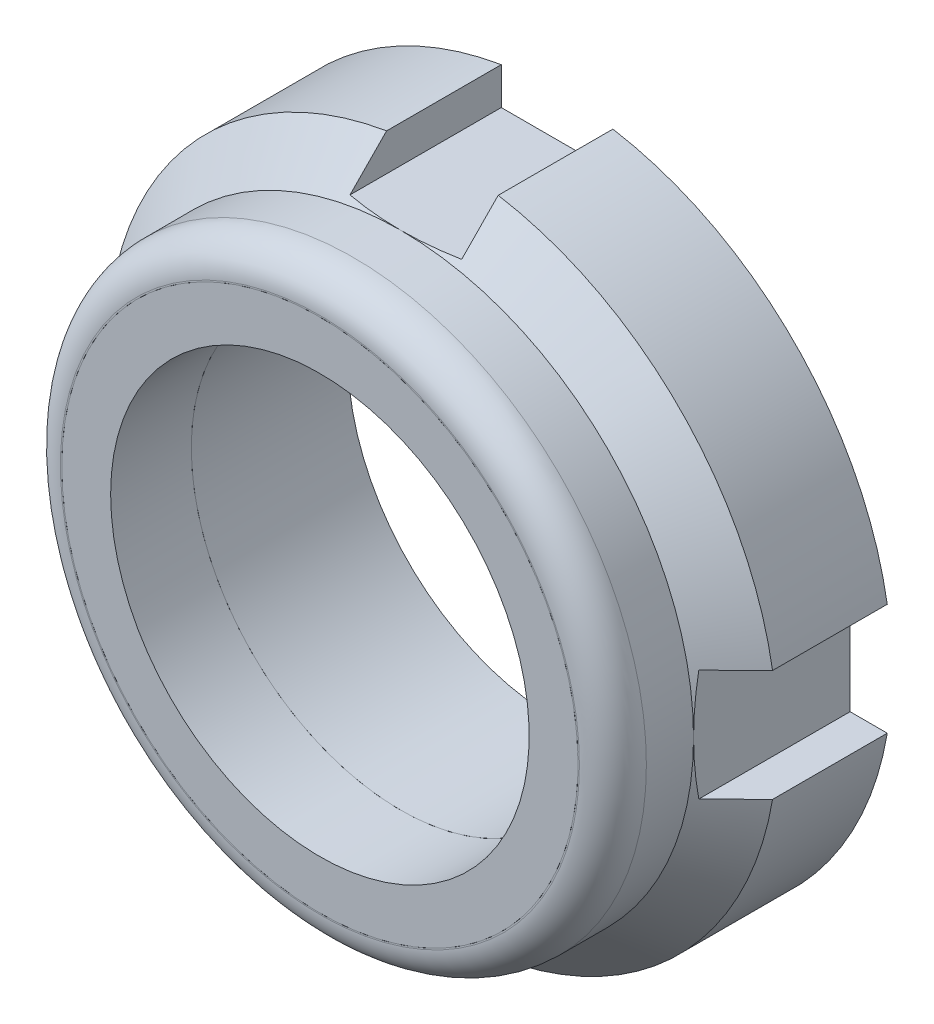
SolidWorks part; units mm, degrees
ref_plane "Front Plane" through (0, 0, 0) normal (0, 0, 1) x (1, 0, 0)
ref_plane "Top Plane" through (0, 0, 0) normal (0, 1, 0) x (1, 0, 0)
ref_plane "Right Plane" through (0, 0, 0) normal (1, 0, 0) x (0, 0, -1)
sketch "Sketch1" plane through (0, 0, 0) normal (0, 0, 1) x (1, 0, 0)
  line L0 (-2, -12) -> (2, -12) construction
  line L1 (0, 0) -> (0, -12) construction
  line L2 (0, 11) -> (0, 7.5) construction
  circle A0 centre (0, 0) radius 12 construction
  circle A1 centre (0, 0) radius 7.5 construction
  circle A2 centre (0, 0) radius 11 construction
  point P9 (0, -10.5)
  point P11 (0, 9.25)
sketch "Sketch2" plane through (0, 0, 0) normal (1, 0, 0) x (0, 0, -1)
  line L0 (-4.25, 0) -> (4.25, 0) construction
  point P2 (0, 0)
  point P3 (-3.75, 0)
  point P5 (-1.36, 0)
  dimension "M" = 5.61
sketch "Sketch4" plane through (0, 0, 0) normal (0, 0, 1) x (1, 0, 0)
  circle A0 centre (0, 0) radius 12 construction
  circle A1 centre (0, 0) radius 12
  circle A2 centre (0, 0) radius 7.5 construction
  circle A3 centre (0, 0) radius 7.5
extrude "Boss-Extrude1" add sketch "Sketch4" along normal up to vertex (4.25 mm away) and the other way up to vertex (4.25 mm away) up to point (0, 0, 4.25) other way up to point (0, 0, -4.25)
sketch "Sketch5" plane through (0, 0, 4.25) normal (0, 0, 1) x (1, 0, 0)
  circle A0 centre (0, 0) radius 11 construction
  circle A1 centre (0, 0) radius 12
  circle A2 centre (0, 0) radius 12
  circle A3 centre (0, 0) radius 11
  dimension "D1" = 0
extrude "Cut-Extrude1" cut sketch "Sketch5" against normal up to vertex (0.5 mm away) up to point (0, 0, 3.75)
sketch "Sketch16" plane through (0, 0, 0) normal (0, 0, 1) x (1, 0, 0)
  line L1 (-2, -10.5) -> (2, -10.5)
  line L2 (-2, -10.5) -> (-2, -12)
  line L3 (-2, -12) -> (2, -12)
  line L4 (2, -10.5) -> (2, -12)
extrude "Cut-Extrude7" cut sketch "Sketch16" against normal through all both and the other way through all
pattern_circular "CirPattern1" count 4 over 360 about axis through (0, 0, 4.25) along (0, 0, -1) of "Cut-Extrude7"
sketch "Sketch18" plane through (0, 0, 0) normal (1, 0, 0) x (0, 0, -1)
  line L0 (-1.36, 10.5) -> (0.14, 12)
  line L2 (0.14, 12) -> (-4.25, 12)
  line L4 (-4.25, 0) -> (4.25, 0) construction
  line L5 (0.14, 12) -> (0, 12) construction
  line L6 (-4.25, 10.5) -> (-1.36, 10.5)
  line L14 (-1.36, 10.5) -> (0.14, 10.5) construction
  line L22 (-4.25, 11) -> (-4.25, -11) construction
  line L23 (-4.25, 10.5) -> (-4.25, 12)
  dimension "D1" = 45
revolve "Cut-Revolve1" cut sketch "Sketch18" angle 360 about L4
fillet "Fillet1" radius 1.2 1 edges at (0, -10.5, 4.25)
sketch "Sketch19" plane through (0, 0, 4.25) normal (0, 0, 1) x (1, 0, 0)
  circle A1 centre (0, 0) radius 9.25
extrude "Cut-Extrude8" cut sketch "Sketch19" against normal up to vertex (2.89 mm away) up to point (0, 10.5, 1.36)
sketch "Sketch20" plane through (0, 0, 1.36) normal (0, 0, 1) x (1, 0, 0)
  circle A0 centre (0, 0) radius 7.5 construction
  circle A1 centre (0, 0) radius 9.25
  circle A2 centre (0, 0) radius 9.25
  circle A3 centre (0, 0) radius 7.5
  dimension "D1" = 0
extrude "Boss-Extrude2" add sketch "Sketch20" along normal up to vertex (2.89 mm away) separate body up to point (0, 0, 4.25)
ref_axis "Center Axis 1" through (0, 0, 0.36) along (0, 0, -1)
ref_plane "Contact Plane 1" through (0, 0, 4.25) normal (0, 0, -1) x (-1, 0, 0)
ref_plane "Contact Plane 2" through (0, 0, -4.25) normal (0, 0, -1) x (-1, 0, 0)
sketch "Sketch8" [suppressed] plane through (0, 0, 4.25) normal (0, 0, 1) x (1, 0, 0)
  circle A0 centre (0, 0) radius 7.5 construction
  circle A1 centre (0, 0) radius 7.5
curve "Helix/Spiral1" [suppressed] pitch 1 height 9.5 turns 9.5 parameters "Pitch"=1
sketch "Sketch14" [suppressed] plane through (0, 0, 4.25) normal (0, 0, 1) x (1, 0, 0)
  circle A0 centre (0, 0) radius 7.5 construction
  circle A4 centre (0, 0) radius 7.5
sketch "Sketch15" [suppressed] plane through (0, 0, -4.25) normal (0, 0, -1) x (-1, 0, 0)
  circle A3 centre (0, 0) radius 7.5 construction
  circle A4 centre (0, 0) radius 7.5
sketch "Sketch9" [suppressed] plane through (0, 0, 0) normal (1, 0, 0) x (0, 0, -1)
  line L0 (-5.1827, 7.6) -> (-5.125, 7.5)
  line L1 (-5.125, 7.5) -> (-4.75, 6.8505)
  line L2 (-4.75, 6.8505) -> (-4.625, 6.8505)
  line L3 (-4.625, 6.8505) -> (-4.25, 7.5)
  line L4 (-4.25, 7.5) -> (-4.1923, 7.6)
  line L5 (-4.1923, 7.6) -> (-5.1827, 7.6)
  line L6 (-4.6875, 7.6) -> (-4.6875, 6.8505) construction
  line L7 (-5.125, 7.5) -> (-4.25, 7.5) construction
  line L8 (-4.9375, 7.1752) -> (-4.4375, 7.1752) construction
  dimension "D1" = 60
  dimension "D2" = 0.1
  dimension "D3" = 0.125
  dimension "D4" = 0.5
sweep "Sweep1" [suppressed] add profiles "Sketch9" path "Helix/Spiral1"
split "Split5" [suppressed] bodies to split 108
split "Split1" [suppressed] bodies to split 127 125
split "Split2" [suppressed] bodies to split 128 125
combine bodies "Combine1" [suppressed] operation type add bodies to combine 110 126
combine bodies "Combine2" [suppressed] operation type add bodies to combine 113 125
extrude "Cut-Extrude5" [suppressed] cut sketch "Sketch14" against normal up to next draft 60
extrude "Cut-Extrude6" [suppressed] cut sketch "Sketch15" against normal up to next draft 60
equation "\"D3@Helix/Spiral1\"=\"Overall Width@Sketch2\"+\"Pitch@Helix/Spiral1\""
equation "\"D3@Sketch9\"=\"Pitch@Helix/Spiral1\"/8"
equation "\"D4@Sketch9\"=\"Pitch@Helix/Spiral1\"/2"
equation "\"M@Sketch2\"=\"Overall Width@Sketch2\"*.66"
equation "\"D1@Fillet1\"=\"OD@Sketch1\"*.05"
